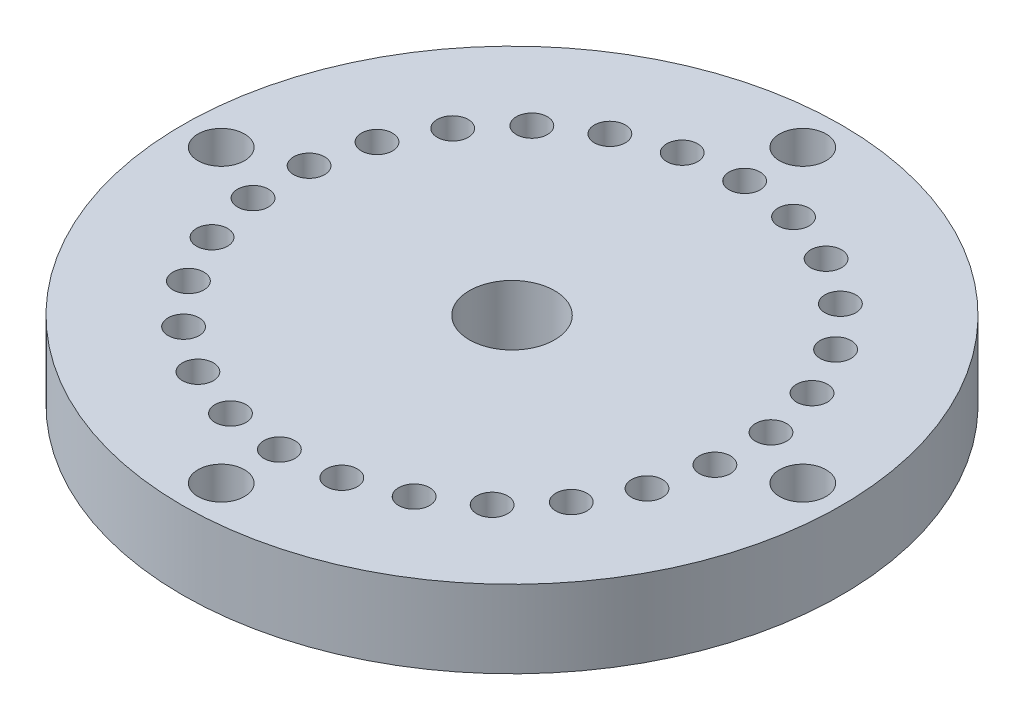
SolidWorks part; units mm, degrees
ref_plane "Plan de face" through (0, 0, 0) normal (0, 0, 1) x (1, 0, 0)
ref_plane "Plan de dessus" through (0, 0, 0) normal (0, 1, 0) x (1, 0, 0)
ref_plane "Plan de droite" through (0, 0, 0) normal (1, 0, 0) x (0, 0, -1)
sketch "Esquisse1" plane through (0, 0, 0) normal (0, 1, 0) x (1, 0, 0)
  circle A0 centre (0, 0) radius 4.25
  circle A1 centre (0, 0) radius 0.55
  circle A2 centre (0, 3) radius 0.2
  circle A3 centre (0, 3.75) radius 0.3
  circle A4 centre (0.7179, 2.9128) radius 0.2
  circle A5 centre (1.3942, 2.6564) radius 0.2
  circle A6 centre (1.9894, 2.2455) radius 0.2
  circle A7 centre (2.469, 1.7042) radius 0.2
  circle A8 centre (2.805, 1.0638) radius 0.2
  circle A9 centre (2.9781, 0.3616) radius 0.2
  circle A10 centre (2.9781, -0.3616) radius 0.2
  circle A11 centre (2.805, -1.0638) radius 0.2
  circle A12 centre (2.469, -1.7042) radius 0.2
  circle A13 centre (1.9894, -2.2455) radius 0.2
  circle A14 centre (1.3942, -2.6564) radius 0.2
  circle A15 centre (0.7179, -2.9128) radius 0.2
  circle A16 centre (0, -3) radius 0.2
  circle A17 centre (-0.7179, -2.9128) radius 0.2
  circle A18 centre (-1.3942, -2.6564) radius 0.2
  circle A19 centre (-1.9894, -2.2455) radius 0.2
  circle A20 centre (-2.469, -1.7042) radius 0.2
  circle A21 centre (-2.805, -1.0638) radius 0.2
  circle A22 centre (-2.9781, -0.3616) radius 0.2
  circle A23 centre (-2.9781, 0.3616) radius 0.2
  circle A24 centre (-2.805, 1.0638) radius 0.2
  circle A25 centre (-2.469, 1.7042) radius 0.2
  circle A26 centre (-1.9894, 2.2455) radius 0.2
  circle A27 centre (-1.3942, 2.6564) radius 0.2
  circle A28 centre (-0.7179, 2.9128) radius 0.2
  circle A29 centre (3.75, 0) radius 0.3
  circle A30 centre (0, -3.75) radius 0.3
  circle A31 centre (-3.75, 0) radius 0.3
  point P64 (0, 0)
  point P70 (0, 0)
  dimension "D1" = 8.5
  dimension "D2" = 1.1
  dimension "D3" = 3
  dimension "D4" = 3.75
  dimension "D5" = 26
extrude "Boss.-Extru.2" add sketch "Esquisse1" along normal blind 1
sketch "Esquisse2" plane through (0, 1, 0) normal (0, 1, 0) x (1, 0, 0)
